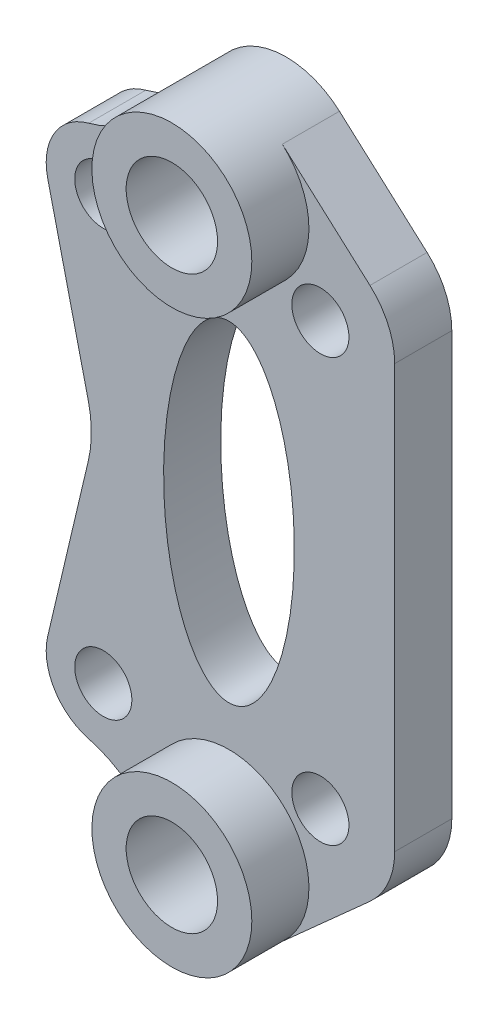
SolidWorks part; units mm, degrees
ref_plane "Front Plane" through (0, 0, 0) normal (0, 0, 1) x (1, 0, 0)
ref_plane "Top Plane" through (0, 0, 0) normal (0, 1, 0) x (1, 0, 0)
ref_plane "Right Plane" through (0, 0, 0) normal (1, 0, 0) x (0, 0, -1)
sketch "Sketch1" plane through (0, 0, 0) normal (0, 0, 1) x (1, 0, 0)
  line L0 (0, 0) -> (23, 0) construction
  line L16 (-15.8665, 17.3525) -> (-12.3159, 2.2951)
  line L17 (-15.8665, -17.3525) -> (-12.3159, -2.2951)
  line L45 (4.6699, 30.2146) -> (12.3397, 23.346)
  line L46 (14.5051, 18.5) -> (14.5051, 0)
  line L47 (14.5051, -18.5) -> (14.5051, 0)
  line L48 (4.6699, -30.2146) -> (12.3397, -23.346)
  circle A14 centre (0, 25) radius 4
  circle A15 centre (0, -25) radius 4
  circle A16 centre (0, 25) radius 7
  circle A17 centre (0, -25) radius 7
  arc A19 (-12.2809, 23.3331) -> (-15.8665, 17.3525) centre (-11, 18.5) ccw
  arc A20 (-6.2238, 28.2038) -> (-12.2809, 23.3331) centre (-14.7327, 32.5837) cw
  arc A21 (-6.2238, -28.2038) -> (-12.2809, -23.3331) centre (-14.7327, -32.5837) ccw
  arc A22 (-12.2809, -23.3331) -> (-15.8665, -17.3525) centre (-11, -18.5) cw
  arc A23 (-12.3159, 2.2951) -> (-12.3159, -2.2951) centre (-22.049, 0) cw
  circle A24 centre (-11, 18.5) radius 2.5
  circle A25 centre (8, 18.5) radius 2.5
  circle A26 centre (-11, -18.5) radius 2.5
  circle A27 centre (8, -18.5) radius 2.5
  arc A28 (12.3397, 23.346) -> (14.5051, 18.5) centre (8, 18.5) cw
  arc A29 (12.3397, -23.346) -> (14.5051, -18.5) centre (8, -18.5) ccw
  ellipse E0 centre (0, 0) end of major axis (0, 14.4669) minor radius 5.7219
  point P0 (-12.2152, 21.7823)
  point P31 (-11.7748, 0)
  dimension "D2" = 11
  dimension "D3" = 5
  dimension "D10" = 8
  dimension "D8" = 37
  dimension "D5" = 10
  dimension "D6" = 5
  dimension "D4" = 50
  dimension "D7" = 19
  dimension "D11" = 3
extrude "Boss-Extrude1" add sketch "Sketch1" along normal blind 5 contours A17 A16 | A16 | A16 A14 | A16 | A16 | A16 | A17 | A17 A15 | A17 | A17 | A17 region at (-14.7078, 20.7229, 0) region at (-1.2347, 31.689, 0) region at (-1.6016, -18.3892, 0)
extrude "Boss-Extrude2" add sketch "Sketch1<8>" along normal blind 10 contours A17 A15 | A16 A14 region at (-1.2347, 31.689, 0) region at (-1.6016, -18.3892, 0)
sketch "Sketch1<8>" plane through (0, 0, 0) normal (0, 0, 1) x (1, 0, 0) same geometry as "Sketch1"
equation "\"in_d\"=40"
equation "\"pipe_thick\"=2"
equation "\"rod_angle\"=20"
equation "\"rod_radius\"=33.5"
equation "\"rod_diameter\"=8"
equation "\"lin_bear_h\"=24"
equation "\"screw_radius\"=40"
equation "\"screw_angle\"=50"
equation "\"lin_bearing_d\"=15"
equation "\"drill_rod_pair\"=37"
equation "\"support_rod_w\"=50"
equation "\"vertical_slider_w\"=65"
equation "\"slope_angle\"=30"
